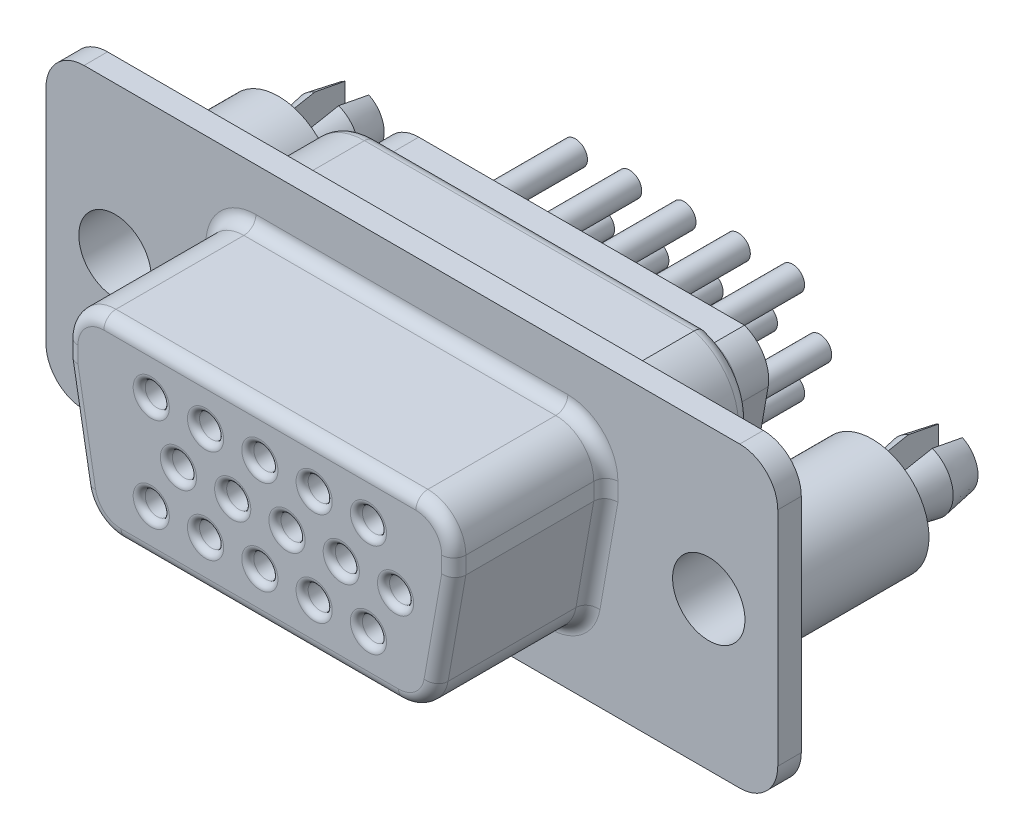
SolidWorks part; units mm, degrees
material "PW60:36:C1:0:1:2:Re:26:"
ref_plane "Plane1" through (0, 0, 0) normal (0, 0, 1) x (1, 0, 0)
ref_plane "Plane2" through (0, 0, 0) normal (0, 1, 0) x (1, 0, 0)
ref_plane "Plane3" through (0, 0, 0) normal (1, 0, 0) x (0, 0, -1)
sketch "Sketch1" plane through (0, 0, 0) normal (0, 0, 1) x (1, 0, 0)
  line L0 (0, 22.5) -> (0, -25) construction
  line L1 (-13.8049, 6.2738) -> (13.8049, 6.2738)
  line L2 (13.8049, -6.2738) -> (-13.8049, -6.2738)
  line L3 (15.4051, -4.6736) -> (15.4051, 4.6736)
  line L4 (-15.4051, -4.6736) -> (-15.4051, 4.6736)
  arc A0 (13.8049, 6.2738) -> (15.4051, 4.6736) centre (13.8049, 4.6736) cw
  arc A1 (13.8049, -6.2738) -> (15.4051, -4.6736) centre (13.8049, -4.6736) ccw
  arc A2 (-15.4051, -4.6736) -> (-13.8049, -6.2738) centre (-13.8049, -4.6736) ccw
  arc A3 (-13.8049, 6.2738) -> (-15.4051, 4.6736) centre (-13.8049, 4.6736) ccw
  point P9 (15.4051, 6.2738)
  point P12 (15.4051, -6.2738)
  point P15 (-15.4051, -6.2738)
  point P18 (-15.4051, 6.2738)
  dimension "D4" = 1.6002
  dimension "D1" = 30.8102
  dimension "D2" = 6.2738
  dimension "D3" = 6.2738
extrude "Base-Extrude" add sketch "Sketch1" against normal blind 0.9906
sketch "Sketch8" plane through (0, 0, 0) normal (0, 0, 1) x (1, 0, 0)
  line L0 (0, 8.3566) -> (0, -9.525) construction
  line L1 (-13.8049, 6.2738) -> (13.8049, 6.2738) construction
  circle A0 centre (12.5, -0.0262) radius 1.524
  circle A1 centre (-12.5, -0.0262) radius 1.524
  dimension "D1" = 3.048
  dimension "D3" = 6.3
  dimension "D2" = 25
extrude "Cut-Extrude4" cut sketch "Sketch8" against normal through all
sketch "Sketch9" plane through (0, 0, 0) normal (0, 0, 1) x (1, 0, 0)
  line L0 (-6.5659, 3.9497) -> (6.5659, 3.9497)
  line L1 (5.8403, -3.9497) -> (-5.8403, -3.9497)
  line L2 (8.1661, 2.3495) -> (8.1661, 1.6256)
  line L3 (-8.1661, 2.3495) -> (-8.1661, 1.6256)
  line L4 (8.1661, 1.6256) -> (7.4162, -2.6274)
  line L5 (-8.1661, 1.6256) -> (-7.4162, -2.6274)
  arc A0 (6.5659, 3.9497) -> (8.1661, 2.3495) centre (6.5659, 2.3495) cw
  arc A1 (-6.5659, 3.9497) -> (-8.1661, 2.3495) centre (-6.5659, 2.3495) ccw
  arc A2 (5.8403, -3.9497) -> (7.4162, -2.6274) centre (5.8403, -2.3495) ccw
  arc A3 (-7.4162, -2.6274) -> (-5.8403, -3.9497) centre (-5.8403, -2.3495) ccw
  dimension "D8" = 1.6002
  dimension "D3" = 1.6002
extrude "Boss-Extrude4" add sketch "Sketch9" along normal blind 6.4008
fillet "Fillet1" radius 0.508 10 edges at (0, 3.9497, 0) (7.6974, 3.481, 0) (8.1661, 1.9875, 0) (7.7911, -0.5009, 0) (6.8689, -3.5753, 0) (0, -3.9497, 0) (-6.8689, -3.5753, 0) (-7.7911, -0.5009, 0) (-8.1661, 1.9875, 0) (-7.6974, 3.481, 0)
fillet "Fillet2" radius 0.508 10 edges at (0, -3.9497, 6.4008) (-6.8689, -3.5753, 6.4008) (-7.7911, -0.5009, 6.4008) (-8.1661, 1.9875, 6.4008) (-7.6974, 3.481, 6.4008) (0, 3.9497, 6.4008) (7.6974, 3.481, 6.4008) (8.1661, 1.9875, 6.4008) (7.7911, -0.5009, 6.4008) (6.8689, -3.5753, 6.4008)
ref_plane "Plane4" through (4.826, 0, 0) normal (1, 0, 0) x (0, 0, -1)
sketch "Sketch13" plane through (0, 0, 6.4008) normal (0, 0, 1) x (1, 0, 0)
  circle A0 centre (0, 1.9812) radius 0.508
  circle A1 centre (0, -1.9812) radius 0.508
  circle A2 centre (2.286, 1.9812) radius 0.508
  circle A3 centre (-2.286, 1.9812) radius 0.508
  circle A4 centre (4.572, 1.9812) radius 0.508
  circle A5 centre (-4.572, 1.9812) radius 0.508
  circle A7 centre (-1.143, 0) radius 0.508
  circle A8 centre (3.429, 0) radius 0.508
  circle A9 centre (1.143, 0) radius 0.508
  circle A10 centre (-3.429, 0) radius 0.508
  circle A11 centre (5.715, 0) radius 0.508
  circle A12 centre (2.286, -1.9812) radius 0.508
  circle A13 centre (-2.286, -1.9812) radius 0.508
  circle A14 centre (4.572, -1.9812) radius 0.508
  circle A15 centre (-4.572, -1.9812) radius 0.508
  point P6 (0, 1.9812)
  point P9 (0, -1.9812)
extrude "Cut-Extrude6" cut sketch "Sketch13" against normal blind 6.4008
sketch "Sketch14" plane through (0, 0, -0.9906) normal (0, 0, -1) x (-1, 0, 0)
  line L12 (6.5943, 4.8387) -> (-7.2836, 4.8387)
  line L13 (8.2917, -2.7817) -> (9.1073, 1.8439)
  line L14 (-5.8403, -4.8387) -> (5.8403, -4.8387)
  line L15 (-9.1171, 1.8996) -> (-8.2917, -2.7817)
  arc A8 (6.5943, 4.8387) -> (9.1073, 1.8439) centre (6.5943, 2.287) cw
  arc A9 (8.2917, -2.7817) -> (5.8403, -4.8387) centre (5.8403, -2.3495) cw
  arc A10 (-5.8403, -4.8387) -> (-8.2917, -2.7817) centre (-5.8403, -2.3495) cw
  arc A11 (-9.1171, 1.8996) -> (-7.2836, 4.8387) centre (-6.5659, 2.3495) cw
extrude "Boss-Extrude5" add sketch "Sketch14" along normal blind 4.1148
sketch "Sketch15" plane through (0, 0, -5.1054) normal (0, 0, -1) x (-1, 0, 0)
  line L16 (-8.1166, 2.0761) -> (-7.2911, -2.6053)
  line L17 (-5.8403, -3.8227) -> (5.8403, -3.8227)
  line L18 (7.2911, -2.6053) -> (8.1067, 2.0203)
  line L19 (6.5943, 3.8227) -> (-7.1218, 3.8227)
  arc A16 (-7.1218, 3.8227) -> (-8.1166, 2.0761) centre (-6.5659, 2.3495) ccw
  arc A17 (-7.2911, -2.6053) -> (-5.8403, -3.8227) centre (-5.8403, -2.3495) ccw
  arc A18 (5.8403, -3.8227) -> (7.2911, -2.6053) centre (5.8403, -2.3495) ccw
  arc A19 (8.1067, 2.0203) -> (6.5943, 3.8227) centre (6.5943, 2.287) ccw
extrude "Boss-Extrude6" add sketch "Sketch15" along normal blind 1.778
sketch "Sketch16" plane through (0, 0, -6.8834) normal (0, 0, -1) x (-1, 0, 0)
  circle A0 centre (-4.572, -1.9812) radius 0.508 construction
  circle A1 centre (-2.286, -1.9812) radius 0.508 construction
  circle A2 centre (0, -1.9812) radius 0.508 construction
  circle A3 centre (2.286, -1.9812) radius 0.508 construction
  circle A4 centre (4.572, -1.9812) radius 0.508 construction
  circle A5 centre (3.429, 0) radius 0.508 construction
  circle A6 centre (1.143, 0) radius 0.508 construction
  circle A7 centre (-1.143, 0) radius 0.508 construction
  circle A8 centre (-3.429, 0) radius 0.508 construction
  circle A9 centre (-5.715, 0) radius 0.508 construction
  circle A10 centre (-4.572, 1.9812) radius 0.508 construction
  circle A11 centre (-2.286, 1.9812) radius 0.508 construction
  circle A12 centre (0, 1.9812) radius 0.508 construction
  circle A13 centre (2.286, 1.9812) radius 0.508 construction
  circle A14 centre (4.572, 1.9812) radius 0.508 construction
  circle A15 centre (-4.572, -1.9812) radius 0.508
  circle A16 centre (-2.286, -1.9812) radius 0.508
  circle A17 centre (0, -1.9812) radius 0.508
  circle A18 centre (2.286, -1.9812) radius 0.508
  circle A19 centre (4.572, -1.9812) radius 0.508
  circle A20 centre (3.429, 0) radius 0.508
  circle A21 centre (1.143, 0) radius 0.508
  circle A22 centre (-1.143, 0) radius 0.508
  circle A23 centre (-3.429, 0) radius 0.508
  circle A24 centre (-5.715, 0) radius 0.508
  circle A25 centre (-4.572, 1.9812) radius 0.508
  circle A26 centre (-2.286, 1.9812) radius 0.508
  circle A27 centre (0, 1.9812) radius 0.508
  circle A28 centre (2.286, 1.9812) radius 0.508
  circle A29 centre (4.572, 1.9812) radius 0.508
extrude "Boss-Extrude7" add sketch "Sketch16" along normal blind 4.572
sketch "Sketch17" plane through (0, 0, -0.9906) normal (0, 0, -1) x (-1, 0, 0)
  circle A0 centre (12.5, -0.0262) radius 2.3876
  circle A1 centre (-12.5, -0.0262) radius 2.3876
  dimension "D1" = 4.7752
extrude "Boss-Extrude8" add sketch "Sketch17" along normal blind 5.8928
sketch "Sketch18" plane through (0, 0, -6.8834) normal (0, 0, -1) x (-1, 0, 0)
  circle A0 centre (12.5, -0.0262) radius 1.016
  circle A1 centre (-12.5, -0.0262) radius 1.016
  dimension "D1" = 2.032
extrude "Boss-Extrude9" add sketch "Sketch18" along normal blind 2.032 draft 10 draft outward yes
sketch "Sketch19" plane through (0, 0, -8.9154) normal (0, 0, -1) x (-1, 0, 0)
  circle A1 centre (-12.5, -0.0262) radius 1.3743
  circle A2 centre (-12.5, -0.0262) radius 1.3743
  circle A3 centre (12.5, -0.0262) radius 1.3743
  circle A4 centre (12.5, -0.0262) radius 1.3743
  dimension "D1" = 0
  dimension "D2" = 0
extrude "Boss-Extrude10" add sketch "Sketch19" along normal blind 1.27 draft 10
sketch "Sketch20" plane through (0, 0, -10.1854) normal (0, 0, -1) x (-1, 0, 0)
  line L0 (-11.992, 1.2508) -> (-11.992, -1.3032)
  line L1 (11.9981, 1.2532) -> (11.9981, -1.3056)
  line L3 (12.9964, -1.3077) -> (12.9964, 1.2553)
  line L5 (-12.9964, 1.2553) -> (-12.9964, -1.3077)
  circle A1 centre (12.5, -0.0262) radius 1.3743 construction
  arc A2 (12.9964, 1.2553) -> (11.9981, 1.2532) centre (12.5, -0.0262) ccw
  circle A3 centre (-12.5, -0.0262) radius 1.3743 construction
  arc A4 (-11.992, 1.2508) -> (-12.9964, 1.2553) centre (-12.5, -0.0262) ccw
  arc A5 (11.9981, -1.3056) -> (12.9964, -1.3077) centre (12.5, -0.0262) ccw
  arc A6 (-12.9964, -1.3077) -> (-11.992, -1.3032) centre (-12.5, -0.0262) ccw
  dimension "D1" = 0.508
extrude "Cut-Extrude7" cut sketch "Sketch20" against normal up to surface (3.302 mm away) up to face at (10.1124, -0.0262, -6.8834)
fillet "Fillet3" radius 0.508 16 edges at (7.7038, -0.2646, -5.1054) (6.7873, -3.478, -5.1054) (0, -3.8227, -5.1054) (-6.7873, -3.478, -5.1054) (-7.6989, -0.2925, -5.1054) (-7.7708, 3.2741, -5.1054) (0.2637, 3.8227, -5.1054) (7.9341, 3.1288, -5.1054) (0.3446, 4.8387, -5.1054) (-8.5491, 3.9272, -5.1054) (-8.6995, -0.4689, -5.1054) (-7.4403, -4.2563, -5.1054) (0, -4.8387, -5.1054) (7.4403, -4.2563, -5.1054) (8.7044, -0.441, -5.1054) (8.7638, 3.7207, -5.1054)
sketch "Sketch21" plane through (0, 0, -0.9906) normal (0, 0, 1) x (1, 0, 0)
  circle A1 centre (-12.5, -0.0262) radius 1.524
  circle A2 centre (-12.5, -0.0262) radius 1.524
  circle A3 centre (12.5, -0.0262) radius 1.524
  circle A4 centre (12.5, -0.0262) radius 1.524
  dimension "D1" = 0
  dimension "D2" = 0
extrude "Cut-Extrude8" cut sketch "Sketch21" against normal blind 3.175
fillet "Fillet4" radius 0.254 15 edges at (6.223, 0, 6.4008) (5.08, -1.9812, 6.4008) (2.794, -1.9812, 6.4008) (3.937, 0, 6.4008) (5.08, 1.9812, 6.4008) (2.794, 1.9812, 6.4008) (0.635, 0, 6.4008) (0.508, -1.9812, 6.4008) (-2.794, -1.9812, 6.4008) (0.508, 1.9812, 6.4008) (-1.651, 0, 6.4008) (-5.08, -1.9812, 6.4008) (-2.921, 0, 6.4008) (-2.794, 1.9812, 6.4008) (-5.08, 1.9812, 6.4008)
